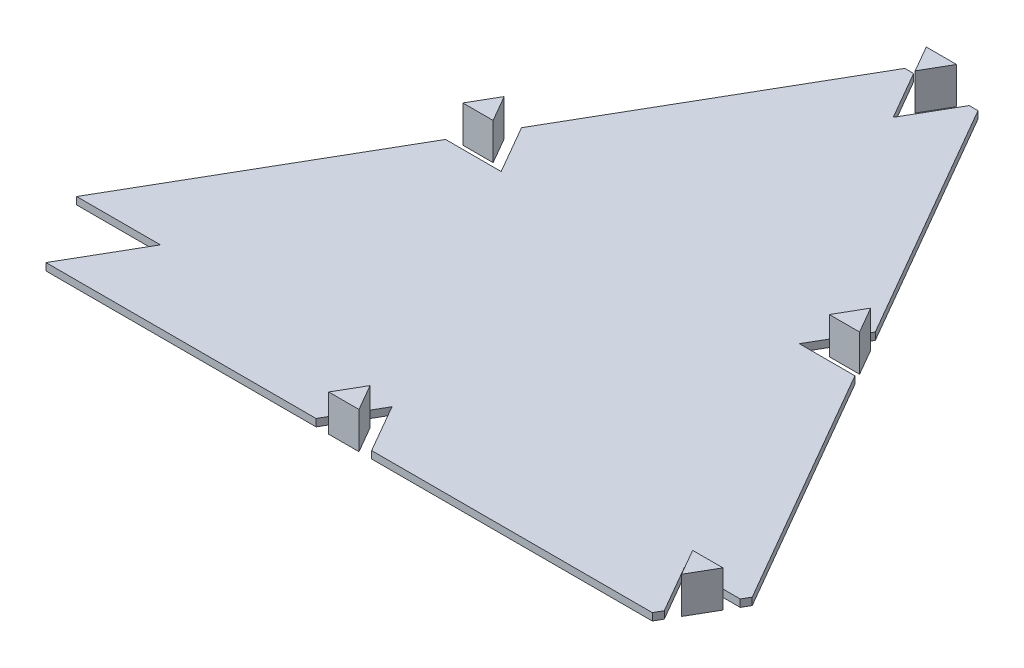
SolidWorks part; units mm, degrees
ref_plane "Front Plane" through (0, 0, 0) normal (0, 0, 1) x (1, 0, 0)
ref_plane "Top Plane" through (0, 0, 0) normal (0, 1, 0) x (1, 0, 0)
ref_plane "Right Plane" through (0, 0, 0) normal (1, 0, 0) x (0, 0, -1)
sketch "Sketch1" plane through (0, 0, 0) normal (0, 1, 0) x (1, 0, 0)
  line L17 (-84.5662, 18.8923) -> (-84.5662, 18.3923) construction
  line L24 (-89.7106, 9.9821) -> (-89.2776, 10.2321) construction
  line L25 (-79.4219, 9.9821) -> (-79.8549, 10.2321) construction
  line L26 (-93.9889, 18.3923) -> (-84.5662, 2.0718)
  line L27 (-84.5662, 2.0718) -> (-75.1436, 18.3923)
  line L28 (-93.9889, 18.3923) -> (-75.1436, 18.3923)
  line L29 (-2.5, 5.4019) -> (-2.067, 5.1519) construction
  line L58 (2.5, 5.4019) -> (2.067, 5.1519) construction
  line L59 (0, 1.0718) -> (0, 1.5718) construction
  line L65 (-4.134, 1.5718) -> (4.134, 1.5718)
  line L66 (-11.7321, 167.8653) -> (11.7321, 167.8653)
  line L67 (97.7417, 18.8923) -> (86.0096, -1.4282)
  line L68 (97.7417, 18.8923) -> (11.7321, 167.8653)
  line L69 (0, 8.7321) -> (4.134, 1.5718)
  line L71 (-4.134, 1.5718) -> (0, 8.7321)
  line L72 (-97.7417, 18.8923) -> (-86.0096, -1.4282)
  line L73 (-86.0096, -1.4282) -> (86.0096, -1.4282)
  line L74 (-97.7417, 18.8923) -> (-11.7321, 167.8653)
  line L79 (87.2106, 14.3122) -> (87.2106, 13.8122) construction
  line L81 (84.7106, 9.9821) -> (85.1436, 10.2321) construction
  line L97 (-94.8549, 18.8923) -> (-84.5662, 1.0718)
  line L100 (-94.8549, 18.8923) -> (-74.2776, 18.8923)
  line L106 (-84.5662, 1.0718) -> (-74.2776, 18.8923)
  line L108 (50.0718, 96.4589) -> (55.0718, 87.7987)
  line L109 (41.6077, 85.7987) -> (56.2265, 85.7987)
  line L111 (50.0718, 96.4589) -> (45.0718, 87.7987)
  line L112 (45.0718, 87.7987) -> (55.0718, 87.7987)
  line L115 (56.2265, 85.7987) -> (94.8549, 18.8923)
  line L116 (48.9171, 98.4589) -> (10.2887, 165.3653)
  line L117 (41.6077, 85.7987) -> (48.9171, 98.4589)
  line L118 (-5, 165.3653) -> (5, 165.3653)
  line L121 (-55.0718, 87.7987) -> (-50.0718, 96.4589)
  line L122 (-5, 165.3653) -> (0, 156.7051)
  line L123 (5, 165.3653) -> (0, 156.7051)
  line L125 (0, 152.7051) -> (7.3094, 165.3653)
  line L126 (0, 152.7051) -> (-7.3094, 165.3653)
  line L127 (-10.2887, 165.3653) -> (-7.3094, 165.3653)
  line L128 (7.3094, 165.3653) -> (10.2887, 165.3653)
  line L129 (-50.0718, 96.4589) -> (-45.0718, 87.7987)
  line L130 (-55.0718, 87.7987) -> (-45.0718, 87.7987)
  line L131 (-48.9171, 98.4589) -> (-10.2887, 165.3653)
  line L132 (-41.6077, 85.7987) -> (-48.9171, 98.4589)
  line L133 (-41.6077, 85.7987) -> (-56.2265, 85.7987)
  line L134 (5, 1.0718) -> (-5, 1.0718)
  line L135 (89.7106, 9.9821) -> (89.2776, 10.2321) construction
  line L136 (-5, 1.0718) -> (0, 9.7321)
  line L137 (0, 9.7321) -> (5, 1.0718)
  line L138 (83.0766, 13.8122) -> (91.3446, 13.8122)
  line L139 (0, 13.7321) -> (-7.3094, 1.0718)
  line L143 (84.5662, 1.0718) -> (7.3094, 1.0718)
  line L144 (0, 13.7321) -> (7.3094, 1.0718)
  line L145 (92.2106, 14.3122) -> (87.2106, 5.6519)
  line L146 (87.2106, 6.6519) -> (91.3446, 13.8122)
  line L147 (87.2106, 5.6519) -> (82.2106, 14.3122)
  line L148 (82.2106, 14.3122) -> (92.2106, 14.3122)
  line L149 (83.0766, 13.8122) -> (87.2106, 6.6519)
  line L150 (94.8549, 18.8923) -> (93.3653, 16.3122)
  line L151 (78.7465, 16.3122) -> (86.0559, 3.6519)
  line L152 (78.7465, 16.3122) -> (93.3653, 16.3122)
  line L153 (86.0559, 3.6519) -> (84.5662, 1.0718)
  line L154 (-82.2568, 1.0718) -> (-7.3094, 1.0718)
  line L155 (-93.7002, 20.8923) -> (-56.2265, 85.7987)
  line L156 (-70.8135, 20.8923) -> (-93.7002, 20.8923)
  line L157 (47.5718, 92.1288) -> (48.0048, 91.8788) construction
  line L158 (52.5718, 92.1288) -> (52.1388, 91.8788) construction
  line L159 (-70.8135, 20.8923) -> (-82.2568, 1.0718)
  line L160 (50.0718, 87.7987) -> (50.0718, 88.2987) construction
  line L161 (45.9378, 88.2987) -> (54.2058, 88.2987)
  line L162 (50.0718, 95.4589) -> (54.2058, 88.2987)
  line L163 (45.9378, 88.2987) -> (50.0718, 95.4589)
  line L164 (0, 165.3653) -> (0, 164.8653) construction
  line L165 (-2.5, 161.0352) -> (-2.067, 161.2852) construction
  line L166 (2.5, 161.0352) -> (2.067, 161.2852) construction
  line L167 (-4.134, 164.8653) -> (4.134, 164.8653)
  line L168 (0, 157.7051) -> (4.134, 164.8653)
  line L169 (-4.134, 164.8653) -> (0, 157.7051)
  line L170 (-52.5718, 92.1288) -> (-52.1388, 91.8788) construction
  line L171 (-47.5718, 92.1288) -> (-48.0048, 91.8788) construction
  line L172 (-50.0718, 87.7987) -> (-50.0718, 88.2987) construction
  line L173 (-54.2058, 88.2987) -> (-45.9378, 88.2987)
  line L174 (-50.0718, 95.4589) -> (-45.9378, 88.2987)
  line L175 (-54.2058, 88.2987) -> (-50.0718, 95.4589)
  line L176 (-76.5352, 10.9821) -> (-76.1021, 10.7321) construction
  line L177 (-69.9474, 21.3923) -> (-81.3908, 1.5718)
  line L178 (-3.6547, 7.4019) -> (-4.0877, 7.6519) construction
  line L179 (0, 14.7321) -> (-7.5981, 1.5718)
  line L180 (-7.5981, 1.5718) -> (-81.3908, 1.5718)
  line L181 (3.6547, 7.4019) -> (4.0877, 7.6519) construction
  line L182 (82.4012, 9.9821) -> (81.9682, 9.7321) construction
  line L183 (0, 14.7321) -> (7.5981, 1.5718)
  line L184 (85.3111, 2.3619) -> (84.878, 2.6119) construction
  line L185 (7.5981, 1.5718) -> (84.2776, 1.5718)
  line L186 (85.4785, 3.6519) -> (84.2776, 1.5718)
  line L187 (77.8805, 16.8122) -> (85.4785, 3.6519)
  line L188 (86.0559, 16.3122) -> (86.0559, 16.8122) construction
  line L189 (94.1101, 17.6022) -> (93.6771, 17.8522) construction
  line L190 (77.8805, 16.8122) -> (93.0766, 16.8122)
  line L191 (94.2776, 18.8923) -> (93.0766, 16.8122)
  line L192 (75.5407, 52.3455) -> (75.1077, 52.0955) construction
  line L193 (55.9378, 85.2987) -> (94.2776, 18.8923)
  line L194 (48.9171, 85.7987) -> (48.9171, 85.2987) construction
  line L195 (40.7417, 85.2987) -> (55.9378, 85.2987)
  line L196 (45.2624, 92.1288) -> (44.8294, 92.3788) construction
  line L197 (29.6029, 131.9121) -> (29.1699, 131.6621) construction
  line L198 (10, 164.8653) -> (48.3397, 98.4589)
  line L199 (40.7417, 85.2987) -> (48.3397, 98.4589)
  line L200 (8.799, 165.3653) -> (8.799, 164.8653) construction
  line L201 (7.5981, 164.8653) -> (10, 164.8653)
  line L202 (3.6547, 159.0352) -> (4.0877, 158.7852) construction
  line L203 (7.5981, 164.8653) -> (0, 151.7051)
  line L204 (-8.799, 165.3653) -> (-8.799, 164.8653) construction
  line L205 (-3.6547, 159.0352) -> (-4.0877, 158.7852) construction
  line L206 (-29.6029, 131.9121) -> (-29.1699, 131.6621) construction
  line L207 (-48.3397, 98.4589) -> (-10, 164.8653)
  line L208 (-10, 164.8653) -> (-7.5981, 164.8653)
  line L209 (0, 151.7051) -> (-7.5981, 164.8653)
  line L210 (-45.2624, 92.1288) -> (-44.8294, 92.3788) construction
  line L211 (-48.3397, 98.4589) -> (-40.7417, 85.2987)
  line L212 (-48.9171, 85.7987) -> (-48.9171, 85.2987) construction
  line L213 (-74.9634, 53.3455) -> (-74.5303, 53.0955) construction
  line L214 (-92.8342, 21.3923) -> (-55.9378, 85.2987)
  line L215 (-55.9378, 85.2987) -> (-40.7417, 85.2987)
  line L216 (-82.2568, 20.8923) -> (-82.2568, 21.3923) construction
  line L217 (-92.8342, 21.3923) -> (-69.9474, 21.3923)
  point P9 (-89.2776, 10.2321)
  point P12 (-79.8549, 10.2321)
  point P15 (-84.5662, 18.3923)
  point P21 (0, 1.5718)
  point P24 (2.067, 5.1519)
  point P27 (-2.067, 5.1519)
  point P32 (87.2106, 13.8122)
  point P36 (89.2776, 10.2321)
  point P41 (85.1436, 10.2321)
  point P48 (50.0718, 88.2987)
  point P51 (50.0718, 88.2987)
  point P54 (52.1388, 91.8788)
  point P58 (48.0048, 91.8788)
  point P74 (0, 164.8653)
  point P89 (2.067, 161.2852)
  point P97 (-2.067, 161.2852)
  point P106 (-50.0718, 88.2987)
  point P109 (-50.0718, 88.2987)
  point P114 (-48.0048, 91.8788)
  point P119 (-52.1388, 91.8788)
  point P122 (0, 0)
  point P123 (-76.1021, 10.7321)
  point P131 (-4.0877, 7.6519)
  point P138 (4.0877, 7.6519)
  point P144 (84.878, 2.6119)
  point P146 (81.9682, 9.7321)
  point P151 (86.0559, 16.8122)
  point P154 (93.6771, 17.8522)
  point P156 (75.1077, 52.0955)
  point P161 (48.9171, 85.2987)
  point P168 (44.8294, 92.3788)
  point P172 (8.799, 164.8653)
  point P176 (4.0877, 158.7852)
  point P184 (-8.799, 164.8653)
  point P187 (-29.1699, 131.6621)
  point P191 (-44.8294, 92.3788)
  point P194 (-48.9171, 85.2987)
  point P198 (-74.5303, 53.0955)
  point P204 (-82.2568, 21.3923)
  dimension "D1" = 0.5
extrude "Boss-Extrude1" add sketch "Sketch1" along normal blind 2 contours L214 L217 L177 L180 L179 L183 L185 L186 L187 L190 L191 L193 L195 L199 L198 L201 L203 L209 L208 L207 L211 L215
extrude "Boss-Extrude2" add sketch "Sketch1<6>" along normal blind 10 separate body contours L71 L65 L69 | L138 L149 L146 | L163 L161 L162 | L175 L173 L174 | L167 L169 L168 region at (0, 0, -3.9585) region at (87.2106, 0, -11.4254) region at (50.0718, 0, -90.6854) region at (0, 0, -162.4786) region at (-50.0718, 0, -90.6854)
sketch "Sketch1<6>" plane through (0, 0, 0) normal (0, 1, 0) x (1, 0, 0) same geometry as "Sketch1"
